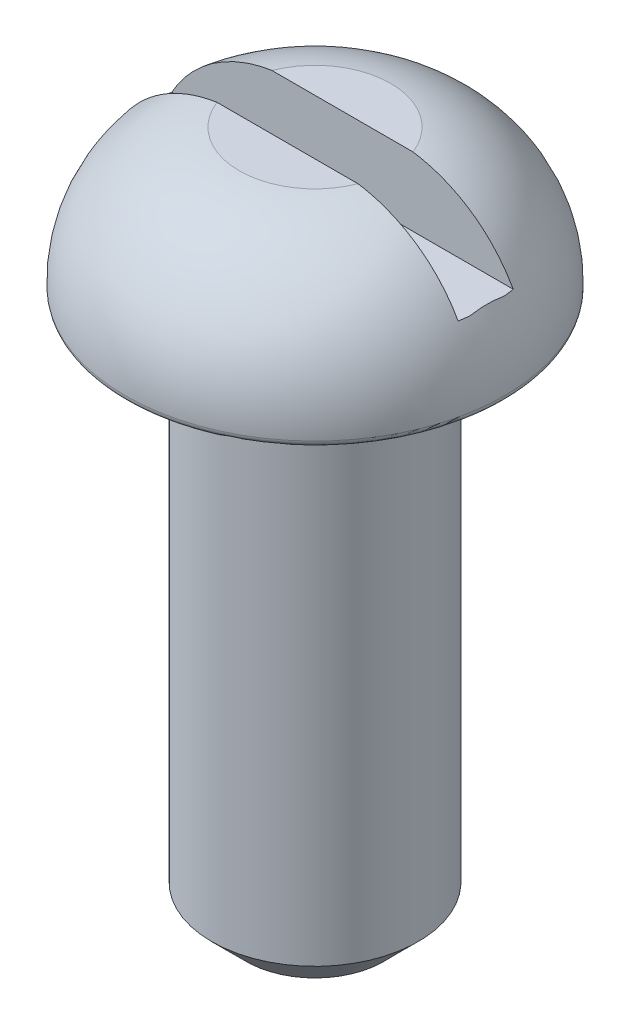
SolidWorks part; units mm, degrees
ref_plane "Спереди" through (0, 0, 0) normal (0, 0, 1) x (1, 0, 0)
ref_plane "Сверху" through (0, 0, 0) normal (0, 1, 0) x (1, 0, 0)
ref_plane "Справа" through (0, 0, 0) normal (1, 0, 0) x (0, 0, -1)
sketch "Эскиз1" plane through (0, 0, 0) normal (0, 0, 1) x (1, 0, 0)
  line L0 (2.75, 7.9) -> (1.5, 7.9)
  line L1 (0, 0) -> (0, 10)
  line L2 (1.5, 7.9) -> (1.5, 0.5)
  line L3 (1.5, 0.5) -> (1, 0)
  line L4 (1, 0) -> (0, 0)
  line L5 (0, 10) -> (1.1, 10)
  arc A0 (1.1, 10) -> (2.75, 7.9) centre (0.7797, 8.0501) cw
  dimension "D2" = 1.1
  dimension "D8" = 2.1
  dimension "D1" = 10
  dimension "D3" = 1.5
  dimension "D4" = 1
  dimension "D5" = 2.1
  dimension "D6" = 2.75
  dimension "D7" = 45
  dimension "D9" = 1.5
revolve "Повернуть1" add sketch "Эскиз1" angle 360 about L1
fillet "Скругление1" radius 0.1 1 edges at (0, 7.9, -2.75)
sketch "Эскиз3" plane through (0, 10, 0) normal (0, 1, 0) x (-1, 0, 0)
  line L1 (2.5, -0.4) -> (-2.5, -0.4)
  line L2 (2.5, -0.4) -> (2.5, 0.4)
  line L3 (2.5, 0.4) -> (-2.5, 0.4)
  line L4 (-2.5, -0.4) -> (-2.5, 0.4)
  dimension "D1" = 0.8
  dimension "D2" = 0.4
  dimension "D3" = 5
  dimension "D4" = 2.5
extrude "Вырез-Вытянуть2" cut sketch "Эскиз3" against normal blind 1
ref_axis "Ось1" through (0, -104.1565, 0) along (0, 1, 0)
